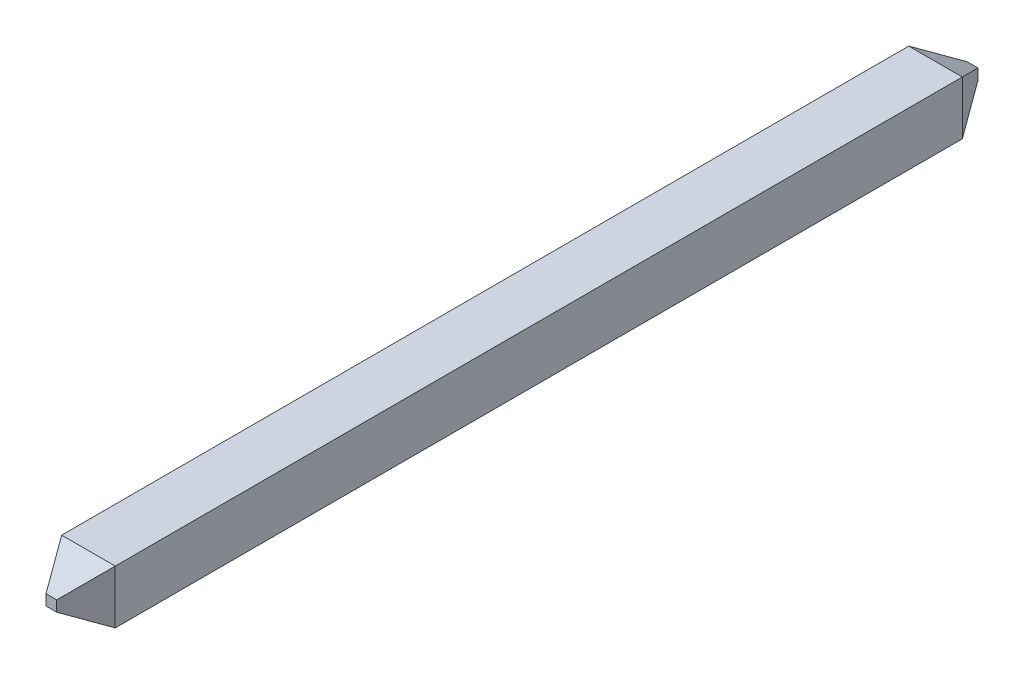
SolidWorks part; units mm, degrees
material "Brass"
ref_plane "Front Plane" through (0, 0, 0) normal (0, 0, 1) x (1, 0, 0)
ref_plane "Top Plane" through (0, 0, 0) normal (0, 1, 0) x (1, 0, 0)
ref_plane "Right Plane" through (0, 0, 0) normal (1, 0, 0) x (0, 0, -1)
sketch "Sketch1" plane through (0, 0, 0) normal (0, 0, 1) x (1, 0, 0)
  line L1 (-0.3175, -0.3175) -> (0.3175, -0.3175)
  line L2 (-0.3175, -0.3175) -> (-0.3175, 0.3175)
  line L3 (-0.3175, 0.3175) -> (0.3175, 0.3175)
  line L4 (0.3175, -0.3175) -> (0.3175, 0.3175)
  line L5 (-0.3175, -0.3175) -> (0.3175, 0.3175) construction
  line L6 (-0.3175, 0.3175) -> (0.3175, -0.3175) construction
  point P0 (0, 0)
  dimension "D1" = 0.635
extrude "Boss-Extrude1" add sketch "Sketch1" along normal blind 10.922
chamfer "Chamfer1" distance 0.254 angle 60 4 edges at (-0.3175, 0, 10.922) (0, 0.3175, 10.922) (0.3175, 0, 10.922) (0, -0.3175, 10.922) first distance on face at (0, 0, 10.922)
chamfer "Chamfer2" distance 0.254 angle 60 4 edges at (0, -0.3175, 0) (-0.3175, 0, 0) (0, 0.3175, 0) (0.3175, 0, 0) first distance on face at (0, 0, 0)
ref_point "Point1"
ref_axis "Axis1" through (0, 0, 10.7197) along (0, 0, 1)
